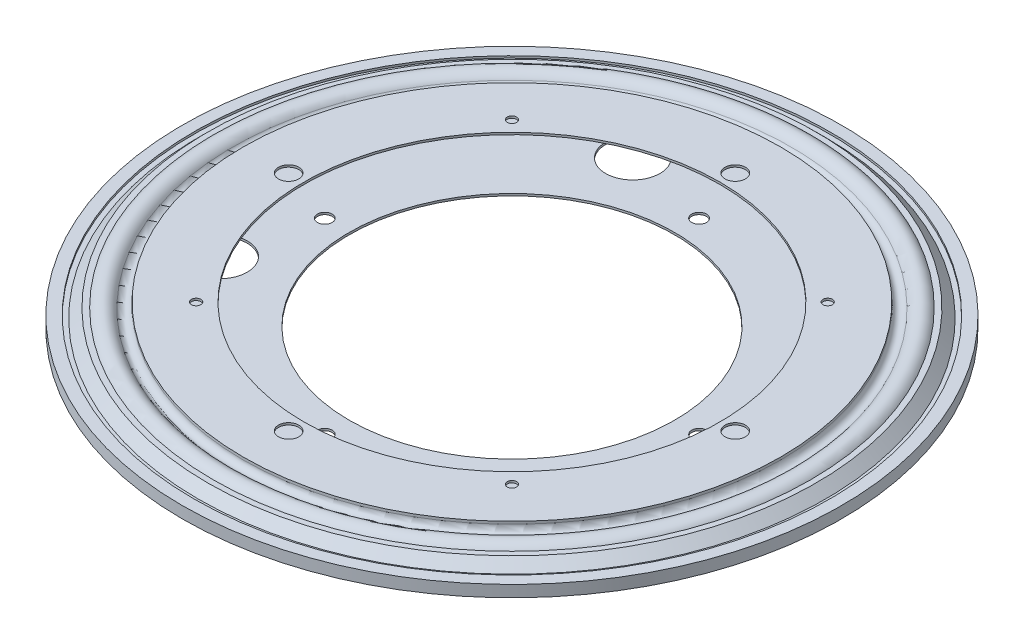
SolidWorks part; units mm, degrees
note: The reader was unsure of these and kept them because the rebuilt part matched: shared geometry of "Sketch1<7>".
ref_plane "Front" through (0, 0, 0) normal (0, 0, 1) x (1, 0, 0)
ref_plane "Top" through (0, 0, 0) normal (0, 1, 0) x (1, 0, 0)
ref_plane "Right" through (0, 0, 0) normal (1, 0, 0) x (0, 0, -1)
sketch "Sketch1" plane through (0, 0, 0) normal (0, 0, 1) x (1, 0, 0)
  line L0 (0, 21.7127) -> (0, -25.7345) construction
  line L1 (101.6, 7.2103) -> (101.6, -7.2103) construction
  line L2 (94.3641, -3.175) -> (94.3641, -4.064)
  line L3 (94.3641, 3.175) -> (94.3641, 4.064)
  line L4 (108.8359, -3.175) -> (108.8359, -4.064)
  line L5 (108.8359, -4.064) -> (115.7605, -4.064)
  line L6 (-2.2827, 0) -> (4.7936, 0) construction
  line L7 (94.3641, 4.064) -> (73.025, 4.064)
  line L8 (115.7605, -4.064) -> (115.7605, 0)
  line L9 (94.3641, -4.064) -> (57.15, -4.064)
  line L10 (87.3679, 0) -> (115.8321, 0) construction
  line L11 (115.7605, 0) -> (111.6965, 0)
  line L12 (113.7285, -0.889) -> (110.0857, -0.889)
  line L13 (110.0857, -0.889) -> (106.8039, 2.3928)
  line L14 (106.8039, 2.3928) -> (104.8849, 2.3928)
  arc A0 (98.1307, -2.1167) -> (94.3641, -3.175) centre (96.3961, -3.175) ccw
  arc A1 (98.1307, -2.1167) -> (105.0693, -2.1167) centre (101.6, 0) ccw
  arc A2 (105.0693, -2.1167) -> (108.8359, -3.175) centre (106.8039, -3.175) cw
  circle A3 centre (101.6, 0) radius 4.064 construction
  arc A4 (98.1307, 2.1167) -> (104.8849, 2.3928) centre (101.6, 0) cw
  arc A6 (98.1307, 2.1167) -> (94.3641, 3.175) centre (96.3961, 3.175) cw
  point P34 (113.7285, 0)
  dimension "D5" = 8.128
  dimension "D7" = 4.064
  dimension "D1" = 114.3
  dimension "D3" = 203.2
  dimension "D4" = 146.05
  dimension "D6" = 8.128
  dimension "D8" = 3.175
  dimension "D9" = 4.064
  dimension "D10" = 0.889
  dimension "D11" = 1.905
  dimension "D12" = 135
revolve "Revolve-Thin1" add sketch "Sketch1" angle 360 about L0
revolve "Revolve-Thin2" add sketch "Sketch1<7>" angle 360 about L0
sketch "Sketch1<7>" plane through (0, 0, 0) normal (0, 0, 1) x (1, 0, 0) same geometry as "Sketch1"
sketch "Sketch2" plane through (0, 0, 0) normal (0, 0, 1) x (1, 0, 0)
  line L0 (101.6, 7.2103) -> (101.6, -7.2103) construction
  line L1 (101.6, 3.2766) -> (101.6, -3.2766)
  line L2 (101.6, 5.3554) -> (101.6, -5.2305) construction
  line L3 (109.5725, -3.3274) -> (-109.5725, -3.3274) construction
  arc A0 (101.6, 3.2766) -> (101.6, -3.2766) centre (101.6, 0) cw
  circle A1 centre (101.6, 0) radius 4.064 construction
  dimension "D1" = 0.0508
revolve "Revolve1" add sketch "Sketch2" angle 360 about L2
pattern_circular "CirPattern1" count 9 over 360 about axis through (0, 0, 0) along (0, 1, 0) of bodies 128
sketch "Sketch3" plane through (0, -3.3274, 0) normal (0, 1, 0) x (-1, 0, 0)
  line L0 (0, 0) -> (0, -83.4152) construction
  line L1 (0, 0) -> (30.0159, -72.4647) construction
  line L2 (-15.4403, -6.3956) -> (15.4403, 6.3956) construction
  circle A0 centre (30.0159, -72.4647) radius 9.525
  dimension "D1" = 19.05
  dimension "D3" = 156.8704
  dimension "D2" = 22.5
extrude "Cut-Extrude1" cut sketch "Sketch3" against normal through all
hole_wizard "9/32 (0.281250) Diameter Hole1" positions "Sketch5" profile "Sketch4" hole size "9/32" standard "Ansi Inch" end condition up to next
sketch "Sketch5" plane through (0, 4.064, 0) normal (0, 1, 0) x (-1, 0, 0)
  line L0 (19.7529, 0) -> (-13.4622, 0) construction
  point P0 (0, -78.4352)
  dimension "D1" = 156.8704
sketch "Sketch4" plane through (0, 4.064, -78.4352) normal (1, 0, 0) x (0, 0, 1)
  line L0 (0, 0) -> (0, 0.7376)
  line L1 (0, 0.7376) -> (3.5719, 0.7376)
  line L2 (3.5719, 0.7376) -> (3.5719, 0)
  line L5 (3.5719, 0) -> (0, 0)
  line L11 (0, -6.35) -> (0, 107.95) construction
  dimension "Thru Hole Dia." = 7.1437
  dimension "Thru Hole Depth" = 0.7376
pattern_circular "CirPattern2" count 4 over 360 about axis through (0, 0, 0) along (0, 1, 0) of "9/32 (0.281250) Diameter Hole1"
hole_wizard "13/64 (0.203130) Diameter Hole1" positions "Sketch7" profile "Sketch6" hole size "13/64" standard "Ansi Inch"
sketch "Sketch7" plane through (0, -3.3274, 0) normal (0, 1, 0) x (-1, 0, 0)
  line L0 (8.178, 0) -> (-7.4231, 0) construction
  point P0 (0, -65.7352)
  dimension "D1" = 131.4704
sketch "Sketch6" plane through (0, -3.3274, -65.7352) normal (1, 0, 0) x (0, 0, 1)
  line L0 (0, 0) -> (0, 9.6781)
  line L1 (0, 9.6781) -> (2.5798, 8.128)
  line L2 (2.5798, 8.128) -> (2.5798, 0)
  line L5 (2.5798, 0) -> (0, 0)
  line L10 (0, 9.6781) -> (-2.5798, 8.128) construction
  line L11 (0, -6.35) -> (0, 107.95) construction
  dimension "Hole Dia." = 5.1595
  dimension "Hole Depth" = 8.128
  dimension "Drill Angle" = 118
pattern_circular "CirPattern3" count 4 over 360 about axis through (0, 0, 0) along (0, 1, 0) of "13/64 (0.203130) Diameter Hole1", "Cut-Extrude1"
hole_wizard "#97 (0.005900) Diameter Hole1" positions "Sketch9" profile "Sketch8" hole size "#97" standard "Ansi Inch" end condition up to next
sketch "Sketch9" plane through (0, 4.064, 0) normal (0, 1, 0) x (-1, 0, 0)
  line L0 (0, 0) -> (55.4621, 55.4621) construction
  line L1 (-9.5024, 9.5024) -> (9.5024, -9.5024) construction
  line L2 (0, 0) -> (0, 39.9168) construction
  point P0 (55.4621, 55.4621)
  dimension "D1" = 45
  dimension "D2" = 156.8704
sketch "Sketch8" plane through (-55.4621, 4.064, 55.4621) normal (1, 0, 0) x (0, 0, 1)
  line L0 (0, 0) -> (0, 0.7376)
  line L1 (0, 0.7376) -> (1.651, 0.7376)
  line L2 (1.651, 0.7376) -> (1.651, 0)
  line L5 (1.651, 0) -> (0, 0)
  line L11 (0, -6.35) -> (0, 107.95) construction
  dimension "Thru Hole Dia." = 3.302
  dimension "Thru Hole Depth" = 0.7376
pattern_circular "CirPattern4" count 4 over 360 about axis through (0, 0, 0) along (0, 1, 0) of "#97 (0.005900) Diameter Hole1"
sketch "Sketch10" plane through (0, 4.064, 0) normal (0, 1, 0) x (1, 0, 0)
  point P0 (0, 78.4352)
  point P1 (0, 0)
equation "\"D7@Sketch1\"=\"D5@Sketch1\"/2"
